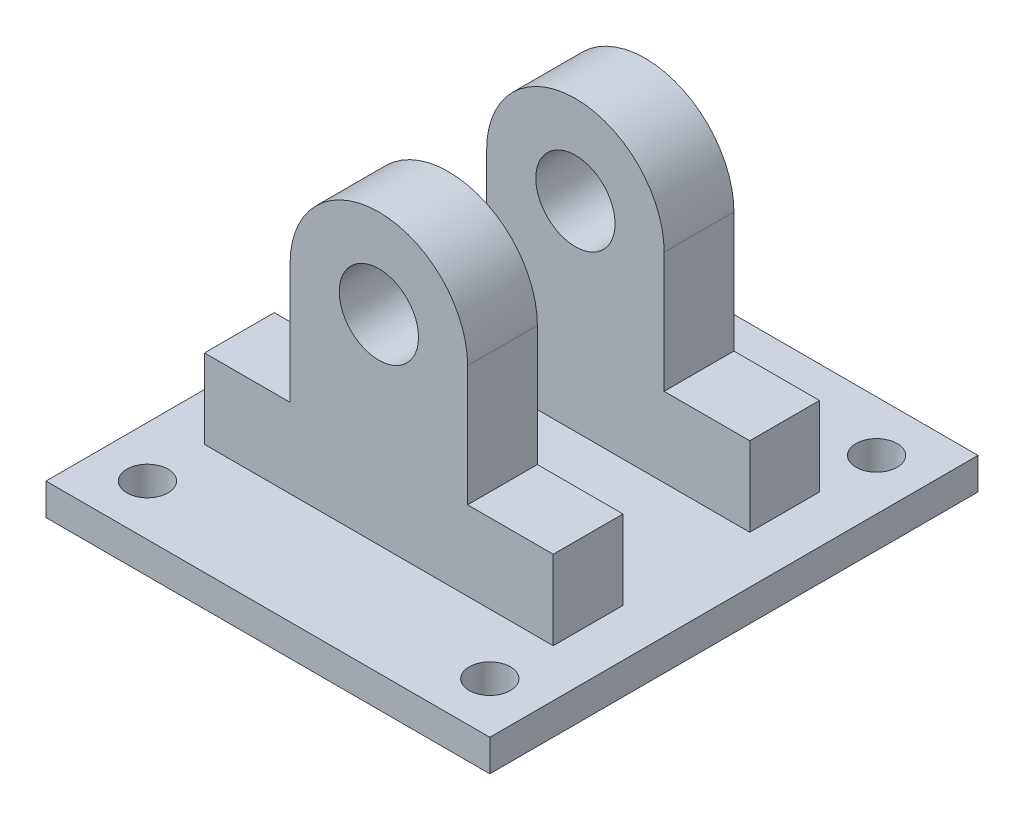
SolidWorks part; units mm, degrees
material "Plain Carbon Steel"
ref_plane "Front Plane" through (0, 0, 0) normal (0, 0, 1) x (1, 0, 0)
ref_plane "Top Plane" through (0, 0, 0) normal (0, 1, 0) x (1, 0, 0)
ref_plane "Right Plane" through (0, 0, 0) normal (1, 0, 0) x (0, 0, -1)
ref_plane "Plane1" through (0, 0, 20) normal (0, 0, 1) x (1, 0, 0)
sketch "Sketch2" plane through (0, 0, 0) normal (0, 0, 1) x (1, 0, 0)
  line L1 (0, 0) -> (850, 0)
  line L2 (0, 0) -> (0, 100)
  line L3 (0, 100) -> (850, 100)
  line L4 (850, 0) -> (850, 100)
  dimension "D1" = 850
  dimension "D2" = 100
sketch "Sketch8" plane through (0, 0, 0) normal (0, 0, 1) x (1, 0, 0)
  line L1 (-70, 150) -> (70, 150)
  line L2 (-70, 150) -> (-70, 160)
  line L3 (-70, 160) -> (70, 160)
  line L4 (70, 150) -> (70, 160)
  line L6 (-70, 0) -> (70, 0)
  line L7 (-70, 0) -> (-70, -10)
  line L8 (-70, -10) -> (70, -10)
  line L9 (70, 0) -> (70, -10)
  line L10 (0, 160) -> (0, -10) construction
  dimension "D1" = 140
  dimension "D2" = 10
  dimension "D3" = 10
  dimension "D5" = 150
extrude "Boss-Extrude6" add sketch "Sketch8" along normal mid plane 154
sketch "Sketch11" plane through (0, 0, 0) normal (0, 0, 1) x (1, 0, 0)
  line L1 (25, 100) -> (175, 100)
  line L2 (25, 100) -> (25, 110)
  line L3 (25, 110) -> (175, 110)
  line L4 (175, 100) -> (175, 110)
  line L6 (25, 0) -> (175, 0)
  line L7 (25, 0) -> (25, -10)
  line L8 (25, -10) -> (175, -10)
  line L9 (175, 0) -> (175, -10)
  line L10 (100, 110) -> (100, -10) construction
  dimension "D1" = 150
  dimension "D2" = 10
  dimension "D3" = 10
sketch "Sketch12" plane through (0, 0, 0) normal (0, 0, 1) x (1, 0, 0)
  line L1 (-70, 150) -> (70, 150)
  line L2 (-70, 150) -> (-70, 190)
  line L3 (-70, 190) -> (70, 190)
  line L4 (70, 150) -> (70, 190)
  line L6 (-70, 0) -> (70, 0)
  line L7 (-70, 0) -> (-70, -10)
  line L8 (-70, -10) -> (70, -10)
  line L9 (70, 0) -> (70, -10)
  line L10 (0, 190) -> (0, -10) construction
  dimension "D1" = 140
  dimension "D2" = 40
  dimension "D3" = 10
  dimension "D5" = 150
extrude "Boss-Extrude8" [suppressed] add sketch "Sketch11" along normal mid plane 170
extrude "Boss-Extrude9" [suppressed] add sketch "Sketch12" along normal mid plane 154
sketch "Sketch9" plane through (0, 0, 0) normal (0, 1, 0) x (1, 0, 0)
  line L0 (0, 0) -> (444.8159, 0) construction
  line L1 (54, 61) -> (54, 0) construction
  line L2 (-54, 61) -> (-54, 0) construction
  line L3 (-70, -77) -> (-70, 77) construction
  line L4 (70, 77) -> (-70, 77) construction
  line L5 (70, -77) -> (70, 77) construction
  circle A0 centre (54, 61) radius 6.5
  circle A1 centre (-54, 61) radius 6.5
  circle A2 centre (-54, -61) radius 6.5
  circle A3 centre (54, -61) radius 6.5
  dimension "D1" = 13
  dimension "D2" = 13
  dimension "D3" = 16
  dimension "D4" = 16
  dimension "D5" = 16
extrude "Cut-Extrude3 (pos 1&2)" cut sketch "Sketch9" against normal blind 160 and the other way blind 160
sketch "Sketch10" plane through (0, 0, 0) normal (0, 1, 0) x (1, 0, 0)
  line L0 (-70, 0) -> (70, 0) construction
  line L1 (54, 61) -> (-54, 61) construction
  line L2 (54, 61) -> (54, -61) construction
  line L3 (54, -61) -> (-54, -61) construction
  line L4 (-54, 61) -> (-54, -61) construction
  line L5 (-70, -77) -> (-70, 77) construction
  line L6 (70, -77) -> (70, 77) construction
  circle A0 centre (54, 61) radius 6
  circle A1 centre (-54, 61) radius 6
  circle A2 centre (-54, -61) radius 6
  circle A3 centre (54, -61) radius 6
  dimension "D1" = 12
extrude "Boss-Extrude7 (pos 1&2)" [suppressed] add sketch "Sketch10" along normal blind 170 and the other way blind 20 separate body
sketch "Sketch3" plane through (0, 0, 20) normal (0, 0, 1) x (1, 0, 0)
  line L0 (0, 160) -> (0, 57.6289) construction
  line L1 (70, 160) -> (-70, 160) construction
  line L2 (870.2621, 160) -> (-104.8876, 160) construction
  line B0 (55, 160) -> (55, 185)
  line B1 (-55, 160) -> (-55, 185)
  line B2 (-28, 185) -> (-28, 223)
  line B3 (28, 185) -> (28, 223)
  arc B4 (-28, 223) -> (28, 223) centre (0, 223) cw
  circle B5 centre (0, 223) radius 12.5
  line B6 (-55, 185) -> (-28, 185)
  line B7 (28, 185) -> (55, 185)
  line B8 (-55, 160) -> (55, 160)
sketch_block_instance "Block1-2"
sketch_block "Block1" parameters "D3"=28, "D4"=25, "D1"=25, "D2"=110, "D5"=38, "D6"=35.7168
extrude "Boss-Extrude2 (pos 1&2)" add sketch "Sketch3" along normal blind 22
ref_plane "Plane2" through (0, 223, 0) normal (0, 1, 0) x (1, 0, 0)
mirror "Mirror4" about plane through (0, 0, 0) normal (0, 0, 1) of "Boss-Extrude2 (pos 1&2)"
sketch "Sketch13" [suppressed] plane through (0, 0, 0) normal (0, 1, 0) x (1, 0, 0)
  line L0 (0, 0) -> (70, 0) construction
  line L1 (54, 61) -> (54, 0) construction
  line L2 (-54, 61) -> (-54, 0) construction
  line L6 (70, 77) -> (-70, 77) construction
  line L7 (-70, -77) -> (-70, 77) construction
  line L8 (70, -77) -> (70, 77) construction
  line L9 (70, -77) -> (70, 77) construction
  circle A0 centre (54, 61) radius 6.5
  circle A1 centre (-54, 61) radius 6.5
  circle A2 centre (-54, -61) radius 6.5
  circle A3 centre (54, -61) radius 6.5
  dimension "D1" = 13
  dimension "D2" = 13
  dimension "D3" = 16
  dimension "D4" = 16
  dimension "D5" = 16
extrude "Cut-Extrude3" [suppressed] cut sketch "Sketch13" against normal through all and the other way through all
sketch "Sketch14" [suppressed] plane through (0, 0, 0) normal (0, 0, 1) x (1, 0, 0)
  line L0 (-70, 0) -> (70, 0) construction
  line L1 (54, 61) -> (-54, 61) construction
  line L2 (54, 61) -> (54, -61) construction
  line L3 (54, -61) -> (-54, -61) construction
  line L4 (-54, 61) -> (-54, -61) construction
  line L7 (70, -77) -> (70, 77) construction
  line L8 (-70, -77) -> (-70, 77) construction
  circle A0 centre (54, 61) radius 6
  circle A1 centre (-54, 61) radius 6
  circle A2 centre (-54, -61) radius 6
  circle A3 centre (54, -61) radius 6
  circle A4 centre (-54, 61) radius 6.5 construction
  circle A5 centre (54, 61) radius 6.5 construction
  dimension "D1" = 12
extrude "Boss-Extrude10" [suppressed] add sketch "Sketch14" along normal blind 220 and the other way blind 30 separate body
sketch "Sketch15" plane through (0, 0, 20) normal (0, 0, 1) x (1, 0, 0)
  line L0 (70, 190) -> (-70, 190) construction
  line L1 (70, 190) -> (-70, 190) construction
  line L2 (0, 190) -> (0, 92.1416) construction
  line B0 (55, 190) -> (55, 215)
  line B1 (-55, 190) -> (-55, 215)
  line B2 (-28, 215) -> (-28, 253)
  line B3 (28, 215) -> (28, 253)
  arc B4 (-28, 253) -> (28, 253) centre (0, 253) cw
  circle B5 centre (0, 253) radius 12.5
  line B6 (-55, 215) -> (-28, 215)
  line B7 (28, 215) -> (55, 215)
  line B8 (-55, 190) -> (55, 190)
sketch_block_instance "Mounting_block-1"
extrude "Boss-Extrude11" [suppressed] add sketch "Sketch15" along normal blind 22
mirror "Mirror2" [suppressed] about plane through (0, 0, 0) normal (0, 0, 1)
ref_plane "Plane3" [suppressed] through (0, 213, 0) normal (0, 1, 0) x (1, 0, 0)
sketch "Sketch16" plane through (0, 0, 20) normal (0, 0, 1) x (1, 0, 0)
  line L1 (-129.585, 50.2557) -> (122.0618, 50.2557)
  line L2 (-129.585, 50.2557) -> (-129.585, -33.4733)
  line L3 (-129.585, -33.4733) -> (122.0618, -33.4733)
  line L4 (122.0618, 50.2557) -> (122.0618, -33.4733)
extrude "Cut-Extrude4" cut sketch "Sketch16" along normal through all and the other way through all
sketch "Sketch17" [suppressed] plane through (0, 0, 20) normal (0, 0, 1) x (1, 0, 0)
  line L1 (-95.61, 26.8143) -> (99.7535, 26.8143)
  line L2 (-95.61, 26.8143) -> (-95.61, -33.9839)
  line L3 (-95.61, -33.9839) -> (99.7535, -33.9839)
  line L4 (99.7535, 26.8143) -> (99.7535, -33.9839)
extrude "Cut-Extrude5" [suppressed] cut sketch "Sketch17" against normal through all and the other way through all
